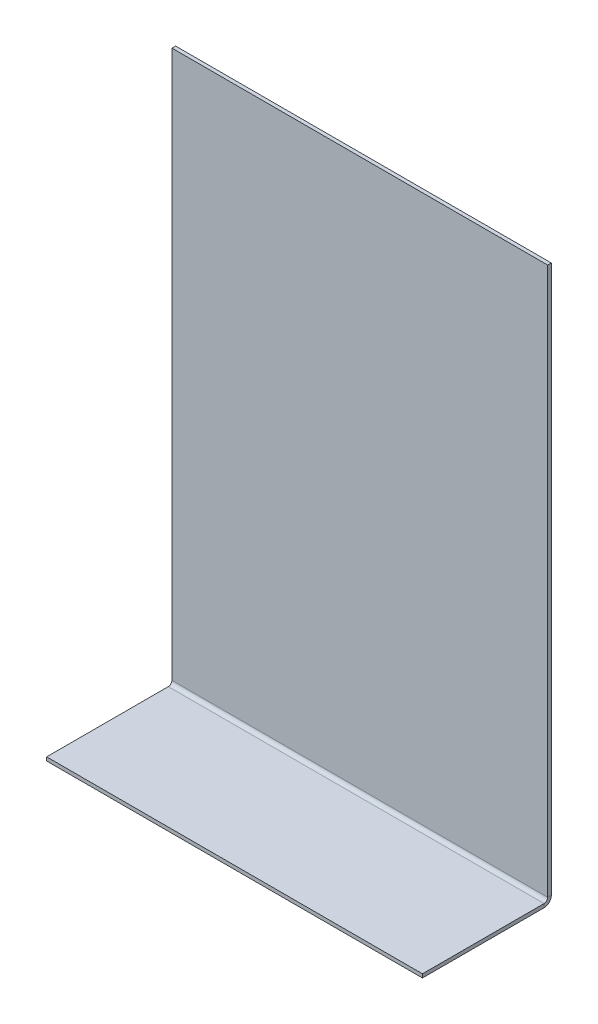
SolidWorks part; units mm, degrees
note: The reader was unsure of these and kept them because the rebuilt part matched: flange length of "Edge-Flange1".
ref_plane "Front Plane" through (0, 0, 0) normal (0, 0, 1) x (1, 0, 0)
ref_plane "Top Plane" through (0, 0, 0) normal (0, 1, 0) x (1, 0, 0)
ref_plane "Right Plane" through (0, 0, 0) normal (1, 0, 0) x (0, 0, -1)
sketch "Sketch1" plane through (0, 0, 0) normal (0, 1, 0) x (1, 0, 0)
  line L1 (0, 0) -> (76.2, 0)
  line L2 (0, 0) -> (0, 25.4)
  line L3 (0, 25.4) -> (76.2, 25.4)
  line L4 (76.2, 0) -> (76.2, 25.4)
  dimension "D1" = 76.2
  dimension "D2" = 25.4
base flange "Base-Flange1" sketch "Sketch1" thickness 0.7366 reverse thickness direction no parameters "D1"=0.7366
edge flange "Edge-Flange1" sketch "Sketch10" flange angle 90 flange length 111.76 flange position material outside bend radius 0.7366 thickness 0.7366 relief rectangular parameters "D6"=10
sketch "Sketch10" plane through (0, 0, -25.4) normal (0, 0, -1) x (-1, 0, 0)
  line L0 (-76.2, 0) -> (0, 0) construction
  line L1 (-76.2, 0) -> (0, 0)
  line L2 (-76.2, 0) -> (-76.2, 111.76)
  line L3 (-76.2, 111.76) -> (0, 111.76)
  line L4 (0, 111.76) -> (0, 0)
bend "EdgeBend1" bend radius 0.7366 bend angle 90 parameters "D5"=1
sketch "Bend-Lines1" plane through (0, 0, 0) normal (0, 1, 0) x (1, 0, 0)
sketch "Bounding-Box1" plane through (0, 0, 0) normal (0, 1, 0) x (1, 0, 0)
sheet metal parameters "Sheet-Metal(1)" thickness 0.7366 parameters "D1"=0.7366
flat pattern "Flat-Pattern(1)" [suppressed]
sketch "Bend-Lines2" plane through (0, 0, 0) normal (0, 1, 0) x (1, 0, 0)
sketch "Bounding-Box2" [suppressed] plane through (0, 0, 0) normal (0, 1, 0) x (1, 0, 0)
sheet metal parameters "Sheet-Metal(2)" thickness 0.7366 parameters "D1"=0.7366
flat pattern "Flat-Pattern(1)"
sketch "Bend-Lines2" plane through (0, 0, 0) normal (0, 1, 0) x (1, 0, 0)
  line L0 (76.2, 38.2312) -> (0, 38.2312) construction
  line L1 (76.2, 38.2312) -> (0, 38.2312) construction
sketch3d "Bounding-Box2" [suppressed]
  line L0 (0, 0, 0) -> (0, 139.9624, 0) construction
  line L1 (76.2, 0, 0) -> (76.2, 139.9624, 0) construction
  line L2 (0, 0, 0) -> (76.2, 0, 0) construction
  line L3 (0, 139.9624, 0) -> (76.2, 139.9624, 0) construction
bend of the flat pattern "Flatten-<EdgeBend1>1"
